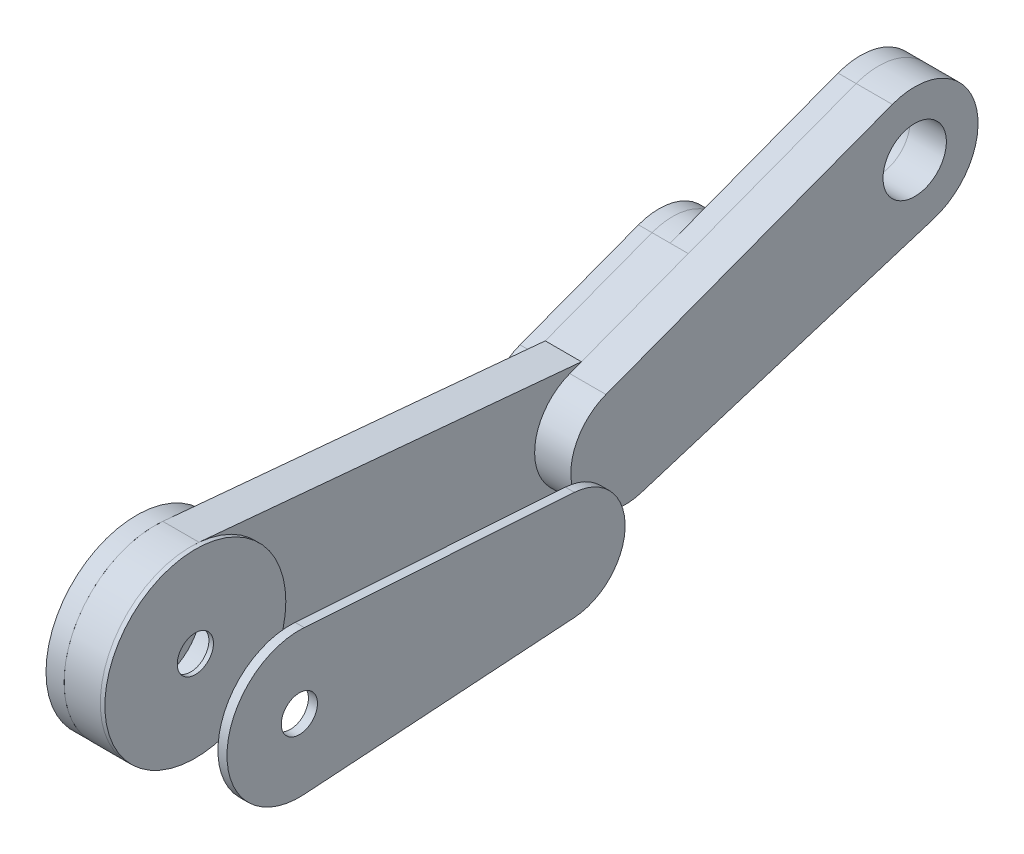
SolidWorks part; units mm, degrees
material "Alum Plate"
ref_plane "Front Plane" through (0, 0, 0) normal (0, 0, 1) x (1, 0, 0)
ref_plane "Top Plane" through (0, 0, 0) normal (0, 1, 0) x (1, 0, 0)
ref_plane "Right Plane" through (0, 0, 0) normal (1, 0, 0) x (0, 0, -1)
other "Bounding Box"
ref_plane "Default Plane" through (-8.9266, -12.7485, 0) normal (-0.1736, 0.9848, 0) x (0.9848, 0.1736, 0)
sketch "Sketch1" plane through (0, 0, 0) normal (1, 0, 0) x (0, 0, -1)
  line L0 (0, 0) -> (-101.6, -34.925)
  line L1 (-101.6, -34.925) -> (-241.3, -34.925)
  circle A0 centre (0, 0) radius 6.35
  circle A1 centre (0, 0) radius 11.1125
  circle A2 centre (-241.3, -34.925) radius 76.2
  circle A4 centre (-241.3, -34.925) radius 6.35
  circle A5 centre (-241.3, -34.925) radius 11.1125
  point P9 (-317.5, -34.925)
  point P11 (-11.1125, 0)
  point P12 (-6.35, 0)
  dimension "D1" = 12.7
  dimension "D2" = 22.225
  dimension "D3" = 152.4
  dimension "D8" = 22.225
  dimension "D5" = 12.7
  dimension "D4" = 139.7
  dimension "D6" = 241.3
  dimension "D7" = 34.925
sketch "Sketch2" plane through (0, 0, 0) normal (0, 1, 0) x (1, 0, 0)
  line L0 (-41.275, -373.5894) -> (-41.275, -0.1795) construction
  line L1 (10.3125, -317.5) -> (0.7875, -317.5)
  line L2 (10.3125, -317.5) -> (10.3125, -165.1)
  line L3 (10.3125, -165.1) -> (0.7875, -165.1)
  line L4 (0.7875, -317.5) -> (0.7875, -165.1)
  line L5 (10.3125, -317.5) -> (0.7875, -165.1) construction
  line L6 (10.3125, -165.1) -> (0.7875, -317.5) construction
  line L7 (41.275, -410.8744) -> (41.275, -23.5487) construction
  line L8 (-41.275, -241.3) -> (0, -241.3) construction
  line L9 (0, -241.3) -> (41.275, -241.3) construction
  line L10 (26.1875, -241.3) -> (0.7875, -241.3)
  line L11 (26.1875, -266.7) -> (10.3125, -266.7)
  line L12 (26.1875, -266.7) -> (26.1875, -215.9)
  line L13 (26.1875, -215.9) -> (10.3125, -215.9)
  line L14 (10.3125, -266.7) -> (10.3125, -215.9)
  line L15 (26.1875, -266.7) -> (10.3125, -215.9) construction
  line L16 (26.1875, -215.9) -> (10.3125, -266.7) construction
  line L22 (13.75, -266.7) -> (22.75, -266.7)
  line L23 (13.75, -266.7) -> (13.75, 19.05)
  line L24 (13.75, 19.05) -> (22.75, 19.05)
  line L25 (-41.275, -6.35) -> (41.275, -6.35)
  line L26 (-41.275, -6.35) -> (-41.275, 6.35)
  line L27 (-41.275, 6.35) -> (41.275, 6.35)
  line L28 (41.275, -6.35) -> (41.275, 6.35)
  line L29 (-41.275, -6.35) -> (41.275, 6.35) construction
  line L30 (-41.275, 6.35) -> (41.275, -6.35) construction
  line L31 (22.75, -266.7) -> (22.75, 19.05)
  line L32 (-41.275, 0) -> (41.275, 0) construction
  line L33 (18.25, 19.05) -> (18.25, -266.7) construction
  line L34 (10.575, 19.05) -> (38.1, 19.05)
  line L35 (10.575, 19.05) -> (10.575, -19.05)
  line L36 (10.575, -19.05) -> (38.1, -19.05)
  line L37 (38.1, 19.05) -> (38.1, -19.05)
  line L38 (10.575, 19.05) -> (38.1, -19.05) construction
  line L39 (10.575, -19.05) -> (38.1, 19.05) construction
  line L40 (30.425, 19.05) -> (30.425, -19.05) construction
  line L45 (25.925, -19.05) -> (34.925, -19.05)
  line L46 (25.925, -19.05) -> (25.925, 19.05)
  line L47 (25.925, 19.05) -> (34.925, 19.05)
  line L48 (34.925, -19.05) -> (34.925, 19.05)
  line L49 (-24.9625, 22.225) -> (-24.9625, -22.225) construction
  line L50 (26.9875, -266.7) -> (30.1625, -266.7)
  line L51 (26.9875, -266.7) -> (26.9875, -76.2)
  line L52 (26.9875, -76.2) -> (30.1625, -76.2)
  line L53 (30.1625, -266.7) -> (30.1625, -76.2)
  line L58 (-35.6375, -22.225) -> (-14.2875, -22.225)
  line L59 (-35.6375, -22.225) -> (-35.6375, 22.225)
  line L60 (-35.6375, 22.225) -> (-14.2875, 22.225)
  line L61 (-14.2875, -22.225) -> (-14.2875, 22.225)
  line L62 (-35.6375, -22.225) -> (-14.2875, 22.225) construction
  line L63 (-35.6375, 22.225) -> (-14.2875, -22.225) construction
  line L64 (-32.4625, -22.225) -> (-17.4625, -22.225)
  line L65 (-32.4625, -22.225) -> (-32.4625, 22.225)
  line L66 (-32.4625, 22.225) -> (-17.4625, 22.225)
  line L67 (-17.4625, -22.225) -> (-17.4625, 22.225)
  line L68 (-7.9375, 22.225) -> (4.7625, 22.225)
  line L69 (-14.2875, 22.225) -> (-7.9375, 22.225)
  line L70 (-14.2875, 22.225) -> (-14.2875, -76.2)
  line L71 (-14.2875, -76.2) -> (-7.9375, -76.2)
  line L72 (-7.9375, 22.225) -> (-7.9375, -76.2)
  line L77 (-7.9375, 22.225) -> (-7.9375, -139.7)
  line L78 (-7.9375, -139.7) -> (4.7625, -139.7)
  line L79 (4.7625, 22.225) -> (4.7625, -139.7)
  line L84 (-7.9375, -76.2) -> (-20.6375, -76.2)
  line L85 (-7.9375, -76.2) -> (-7.9375, -273.05)
  line L86 (-7.9375, -273.05) -> (-20.6375, -273.05)
  line L87 (-20.6375, -76.2) -> (-20.6375, -273.05)
  line L88 (-20.6375, -139.7) -> (-25.4, -139.7)
  line L89 (-20.6375, -139.7) -> (-20.6375, -76.2)
  line L90 (-20.6375, -76.2) -> (-25.4, -76.2)
  line L91 (-25.4, -139.7) -> (-25.4, -76.2)
  line L92 (-20.6375, -273.05) -> (-26.9875, -273.05)
  line L93 (-20.6375, -273.05) -> (-20.6375, -209.55)
  line L94 (-20.6375, -209.55) -> (-26.9875, -209.55)
  line L95 (-26.9875, -273.05) -> (-26.9875, -209.55)
  line L96 (-7.9375, -273.05) -> (-6.3373, -273.05)
  line L97 (-7.9375, -273.05) -> (-7.9375, -209.55)
  line L98 (-7.9375, -209.55) -> (-6.3373, -209.55)
  line L99 (-6.3373, -273.05) -> (-6.3373, -209.55)
  line L100 (-9.525, -257.97) -> (-20.6375, -257.97)
  line L101 (-9.525, -257.97) -> (-9.525, -224.63)
  line L102 (-9.525, -224.63) -> (-20.6375, -224.63)
  line L103 (-20.6375, -257.97) -> (-20.6375, -224.63)
  line L104 (-9.525, -257.97) -> (-20.6375, -224.63) construction
  line L105 (-9.525, -224.63) -> (-20.6375, -257.97) construction
  point P0 (5.55, -241.3)
  point P19 (18.25, -241.3)
  point P31 (24.3375, 0)
  point P34 (0, 0)
  point P57 (-24.9625, 0)
  point P75 (-26.9875, -241.3)
  point P81 (-15.0812, -241.3)
  dimension "D1" = 9.525
  dimension "D2" = 82.55
  dimension "D3" = 15.875
  dimension "D4" = 50.8
  dimension "D5" = 9
  dimension "D6" = 12.7
  dimension "D7" = 38.1
  dimension "D8" = 3.175
  dimension "D9" = 3.175
  dimension "D10" = 3.175
  dimension "D11" = 3.175
  dimension "D12" = 3.175
  dimension "D13" = 15
  dimension "D14" = 3.175
  dimension "D15" = 6.35
  dimension "D16" = 44.45
  dimension "D17" = 12.7
  dimension "D18" = 4.7625
  dimension "D19" = 34.925
  dimension "D20" = 25.4
  dimension "D21" = 38.1
  dimension "D22" = 63.5
  dimension "D23" = 12.7
  dimension "D24" = 6.35
  dimension "D25" = 1.6002
  dimension "D26" = 33.34
  dimension "D27" = 11.1125
  dimension "D28" = 63.5
  dimension "D29" = 4.7625
sketch "Sketch3" plane through (0, 0, 0) normal (1, 0, 0) x (0, 0, -1)
  line L0 (-108.3225, -17.1006) -> (-7.8429, 20.7952)
  line L1 (-95.9423, -53.1155) -> (6.6006, -21.2222)
  arc A0 (-7.8429, 20.7952) -> (6.6006, -21.2222) centre (0, 0) cw
  arc A1 (-108.3225, -17.1006) -> (-95.9423, -53.1155) centre (-101.6, -34.925) ccw
  circle A2 centre (0, 0) radius 11.1125 construction
  circle A3 centre (0, 0) radius 11.1125
  point P8 (22.225, 0)
  point P9 (0, 0)
  dimension "D1" = 19.05
extrude "Boss-Extrude1" add sketch "Sketch3" along normal up to vertex (4.7625 mm away) and the other way up to vertex (7.9375 mm away) up to point (4.7625, 0, -22.225) other way up to point (-7.9375, 0, -22.225)
sketch "Sketch4" plane through (-7.9375, 0, 0) normal (-1, 0, 0) x (0, 0, 1)
  line L0 (0, 0) -> (101.6, -34.925) construction
  line L1 (7.8429, 20.7952) -> (108.3225, -17.1006) construction
  line L2 (95.9423, -53.1155) -> (-6.6006, -21.2222) construction
  line L3 (53.5164, -39.92) -> (95.9423, -53.1155)
  line L5 (99.8682, -53.8961) -> (238.4136, -66.5435)
  line L8 (66.7503, -1.4216) -> (104.2271, -15.556)
  line L9 (104.2271, -15.556) -> (238.4136, -3.3065)
  arc A0 (66.7503, -1.4216) -> (53.5164, -39.92) centre (59.5642, -20.4752) ccw
  arc A1 (95.9423, -53.1155) -> (108.3225, -17.1006) centre (101.6, -34.925) ccw construction
  arc A2 (95.9423, -53.1155) -> (99.8682, -53.8961) centre (101.6, -34.925) ccw
  arc A3 (238.4136, -3.3065) -> (238.4136, -66.5435) centre (241.3, -34.925) cw
  circle A4 centre (241.3, -34.925) radius 16.67
  point P13 (273.05, -34.925)
  point P22 (257.97, -34.925)
  point P26 (0, 0)
  dimension "D1" = 44.45
extrude "Boss-Extrude2" add sketch "Sketch4" along normal up to vertex (12.7 mm away) separate body up to point (-20.6375, 0, 76.2)
sketch "Sketch5" plane through (-7.9375, 0, 0) normal (-1, 0, 0) x (0, 0, 1)
  line L2 (-6.6006, -21.2222) -> (95.9423, -53.1155)
  line L3 (108.3225, -17.1006) -> (7.8429, 20.7952)
  line L4 (-6.6006, -21.2222) -> (53.5164, -39.92)
  line L5 (66.7503, -1.4216) -> (7.8429, 20.7952)
  arc A0 (66.7503, -1.4216) -> (53.5164, -39.92) centre (59.5642, -20.4752) ccw construction
  arc A1 (66.7503, -1.4216) -> (53.5164, -39.92) centre (59.5642, -20.4752) ccw
  arc A2 (7.8429, 20.7952) -> (-6.6006, -21.2222) centre (0, 0) ccw
  arc A3 (95.9423, -53.1155) -> (108.3225, -17.1006) centre (101.6, -34.925) ccw
  arc A4 (7.8429, 20.7952) -> (-6.6006, -21.2222) centre (0, 0) ccw
  circle A6 centre (0, 0) radius 11.1125 construction
  circle A7 centre (0, 0) radius 11.1125
  dimension "D1" = 0
extrude "Boss-Extrude3" add sketch "Sketch5" along normal up to vertex (6.35 mm away) separate body up to point (-14.2875, 0, -22.225)
sketch "Sketch6" plane through (-20.6375, 0, 0) normal (-1, 0, 0) x (0, 0, 1)
  circle A0 centre (241.3, -34.925) radius 31.75
  arc A1 (238.4136, -66.5435) -> (238.4136, -3.3065) centre (241.3, -34.925) ccw construction
  circle A2 centre (241.3, -34.925) radius 6.35 construction
  circle A3 centre (241.3, -34.925) radius 6.35
extrude "Boss-Extrude4" add sketch "Sketch6" along normal up to vertex (6.35 mm away) separate body up to point (-26.9875, 0, 273.05)
sketch "Sketch7" plane through (-7.9375, 0, 0) normal (1, 0, 0) x (0, 0, -1)
  circle A0 centre (-241.3, -34.925) radius 31.75
  circle A1 centre (-241.3, -34.925) radius 6.35 construction
  circle A2 centre (-241.3, -34.925) radius 6.35
  arc A3 (-238.4136, -3.3065) -> (-238.4136, -66.5435) centre (-241.3, -34.925) ccw construction
extrude "Boss-Extrude5" add sketch "Sketch7" along normal up to vertex (1.6002 mm away) separate body up to point (-6.3373, 0, 273.05)
sketch "Sketch8" plane through (-20.6375, 0, 0) normal (-1, 0, 0) x (0, 0, 1)
  line L0 (53.5164, -39.92) -> (95.9423, -53.1155) construction
  line L2 (53.5164, -39.92) -> (95.9423, -53.1155)
  line L3 (66.7503, -1.4216) -> (108.3225, -17.1006)
  arc A0 (66.7503, -1.4216) -> (53.5164, -39.92) centre (59.5642, -20.4752) ccw construction
  arc A1 (66.7503, -1.4216) -> (53.5164, -39.92) centre (59.5642, -20.4752) ccw
  arc A2 (95.9423, -53.1155) -> (108.3225, -17.1006) centre (101.6, -34.925) ccw
  point P2 (93.5642, -64.9039)
extrude "Boss-Extrude6" add sketch "Sketch8" along normal up to vertex (4.7625 mm away) separate body up to point (-25.4, 0, 76.2)
sketch "Sketch9" plane through (4.7625, 0, 0) normal (1, 0, 0) x (0, 0, -1)
  line L0 (-104.2271, -15.556) -> (-101.6, -34.925) construction
  line L2 (-236.639, -6.7327) -> (-104.3427, -28.6052) construction
  line L3 (-100.1623, -27.8569) -> (-12.5783, 22.0668) construction
  line L4 (-236.8389, -63.1496) -> (-100.6906, -41.6303) construction
  line L5 (-100.6906, -41.6303) -> (3.9654, -25.0885) construction
  circle A0 centre (-103.3069, -22.3402) radius 2.3813
  circle A2 centre (-103.3069, -22.3402) radius 6.35 construction
  circle A5 centre (-241.3, -34.925) radius 28.575 construction
  circle A6 centre (0, 0) radius 25.4 construction
  point P2 (-97.5643, -50.2428)
  point P3 (0, 0)
  dimension "D1" = 12.7
  dimension "D2" = 4.7625
  dimension "D5" = 57.15
  dimension "D6" = 50.8
  dimension "D4" = 12.7
sketch "Sketch10" plane through (0, 0, 0) normal (1, 0, 0) x (0, 0, -1)
  line L0 (-101.6, -34.925) -> (-241.3, -34.925) construction
  line L1 (-239.6067, -9.5815) -> (-144.78, -15.9174)
  line L2 (-144.78, -53.9326) -> (-239.6067, -60.2685)
  arc A0 (-239.6067, -9.5815) -> (-239.6067, -60.2685) centre (-241.3, -34.925) ccw
  arc A1 (-144.78, -53.9326) -> (-144.78, -15.9174) centre (-146.05, -34.925) ccw
  circle A2 centre (-241.3, -34.925) radius 6.35 construction
  circle A3 centre (-241.3, -34.925) radius 6.35
  point P9 (-266.7, -34.925)
  point P10 (0, 0)
  point P12 (-144.6378, -47.625)
  dimension "D1" = 19.05
  dimension "D2" = 95.25
extrude "Boss-Extrude7" add sketch "Sketch10" along normal up to vertex (30.1625 mm away) from vertex separate body up to point (30.1625, 0, 266.7) starting at point (26.9875, 0, 266.7)
